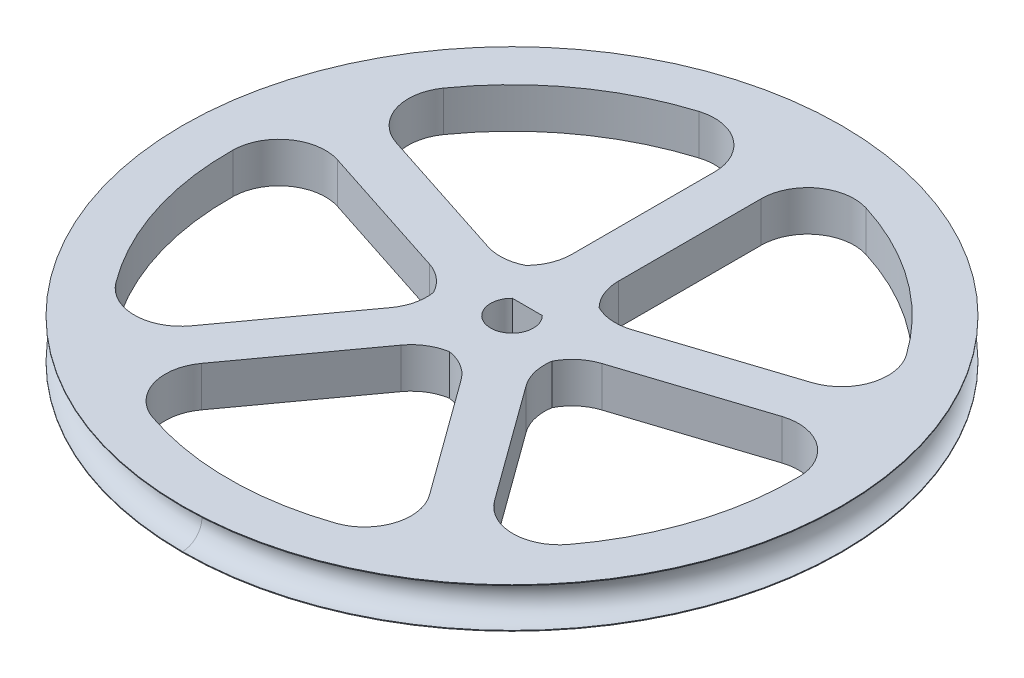
SolidWorks part; units mm, degrees
ref_plane "Front Plane" through (0, 0, 0) normal (0, 0, 1) x (1, 0, 0)
ref_plane "Top Plane" through (0, 0, 0) normal (0, 1, 0) x (1, 0, 0)
ref_plane "Right Plane" through (0, 0, 0) normal (1, 0, 0) x (0, 0, -1)
sketch "Sketch1" plane through (0, 0, 0) normal (0, 1, 0) x (1, 0, 0)
  line L1 (0, 0) -> (0, 72) construction
  line L2 (0, 0) -> (-68.4761, 22.2492) construction
  line L3 (0, 0) -> (22.0431, 7.1622) construction
  line L4 (0, 0) -> (-13.6234, -18.751) construction
  line L5 (0, 0) -> (13.6234, -18.751) construction
  line L6 (-1.905, 23.0991) -> (-1.905, 4.7093)
  line L7 (1.905, 23.0991) -> (1.905, 4.7093)
  line L8 (-3.8901, 3.267) -> (-21.3799, 8.9498)
  line L9 (-22.5572, 5.3262) -> (-5.0675, -0.3565)
  line L10 (-4.3092, -2.6902) -> (-15.1185, -17.5678)
  line L11 (-1.2269, -4.9296) -> (-12.0361, -19.8073)
  line L12 (3.8901, 3.267) -> (21.3799, 8.9498)
  line L13 (22.5572, 5.3262) -> (5.0675, -0.3565)
  line L14 (4.3092, -2.6902) -> (15.1185, -17.5678)
  line L15 (1.2269, -4.9296) -> (12.0361, -19.8073)
  line L16 (-1.2264, 1.254) -> (1.2264, 1.254)
  arc A1 (-5.0675, -0.3565) -> (-4.3092, -2.6902) centre (0, 0) ccw
  circle A2 centre (0, 0) radius 26.9875
  arc A3 (-22.5572, 5.3262) -> (-15.1185, -17.5678) centre (0, 0) ccw
  arc A4 (-1.905, 4.7093) -> (-3.8901, 3.267) centre (0, 0) ccw
  arc A5 (3.8901, 3.267) -> (1.905, 4.7093) centre (0, 0) ccw
  arc A6 (-1.905, 23.0991) -> (-21.3799, 8.9498) centre (0, 0) ccw
  arc A7 (-12.0361, -19.8073) -> (12.0361, -19.8073) centre (0, 0) ccw
  arc A8 (-1.2269, -4.9296) -> (1.2269, -4.9296) centre (0, 0) ccw
  arc A9 (4.3092, -2.6902) -> (5.0675, -0.3565) centre (0, 0) ccw
  arc A10 (21.3799, 8.9498) -> (1.905, 23.0991) centre (0, 0) ccw
  arc A11 (15.1185, -17.5678) -> (22.5572, 5.3262) centre (0, 0) ccw
  arc A12 (-1.2264, 1.254) -> (1.2264, 1.254) centre (0, 0) ccw
  dimension "D3" = 5.08
  dimension "D4" = 26.9875
  dimension "D5" = 23.1775
  dimension "D6" = 72
  dimension "D12" = 1.905
  dimension "D20" = 3.508
  dimension "D21" = 1.254
  dimension "D7" = 72
  dimension "D8" = 72
  dimension "D9" = 72
  dimension "D10" = 1.905
  dimension "D11" = 1.905
  dimension "D13" = 1.905
  dimension "D14" = 1.905
  dimension "D15" = 1.905
  dimension "D16" = 1.905
  dimension "D17" = 1.905
  dimension "D18" = 1.905
  dimension "D19" = 1.905
extrude "Boss-Extrude1" add sketch "Sketch1" along normal blind 3.302 contours A2 A11 L14 A9 L13 A10 L12 A5 L7 A6 L6 A4 L8 A3 L9 A1 L10 A12 L11 A8 L15 A7
fillet "Fillet1" radius 3.81 20 edges at (-22.5572, 1.651, -5.3262) (-5.0675, 1.651, 0.3565) (-4.3092, 1.651, 2.6902) (-15.1185, 1.651, 17.5678) (12.0361, 1.651, 19.8073) (1.2269, 1.651, 4.9296) (-1.2269, 1.651, 4.9296) (-12.0361, 1.651, 19.8073) (15.1185, 1.651, 17.5678) (22.5572, 1.651, -5.3262) (5.0675, 1.651, 0.3565) (21.3799, 1.651, -8.9498) (3.8901, 1.651, -3.267) (4.3092, 1.651, 2.6902) (1.905, 1.651, -4.7093) (-21.3799, 1.651, -8.9498) (-3.8901, 1.651, -3.267) (-1.905, 1.651, -4.7093) (1.905, 1.651, -23.0991) (-1.905, 1.651, -23.0991)
sketch "Sketch2" plane through (0, 0, 0) normal (1, 0, 0) x (0, 0, -1)
  line L0 (26.9875, 0) -> (26.9875, 3.302) construction
  line L1 (0, 0) -> (0, 10) construction
  circle A0 centre (26.9875, 1.651) radius 1.5875
  dimension "D1" = 1.5875
  dimension "D2" = 26.9875
  dimension "D3" = 1.651
sweep "Cut-Sweep1" cut profiles "Sketch2" path edge at (0, 0, 26.9875)
